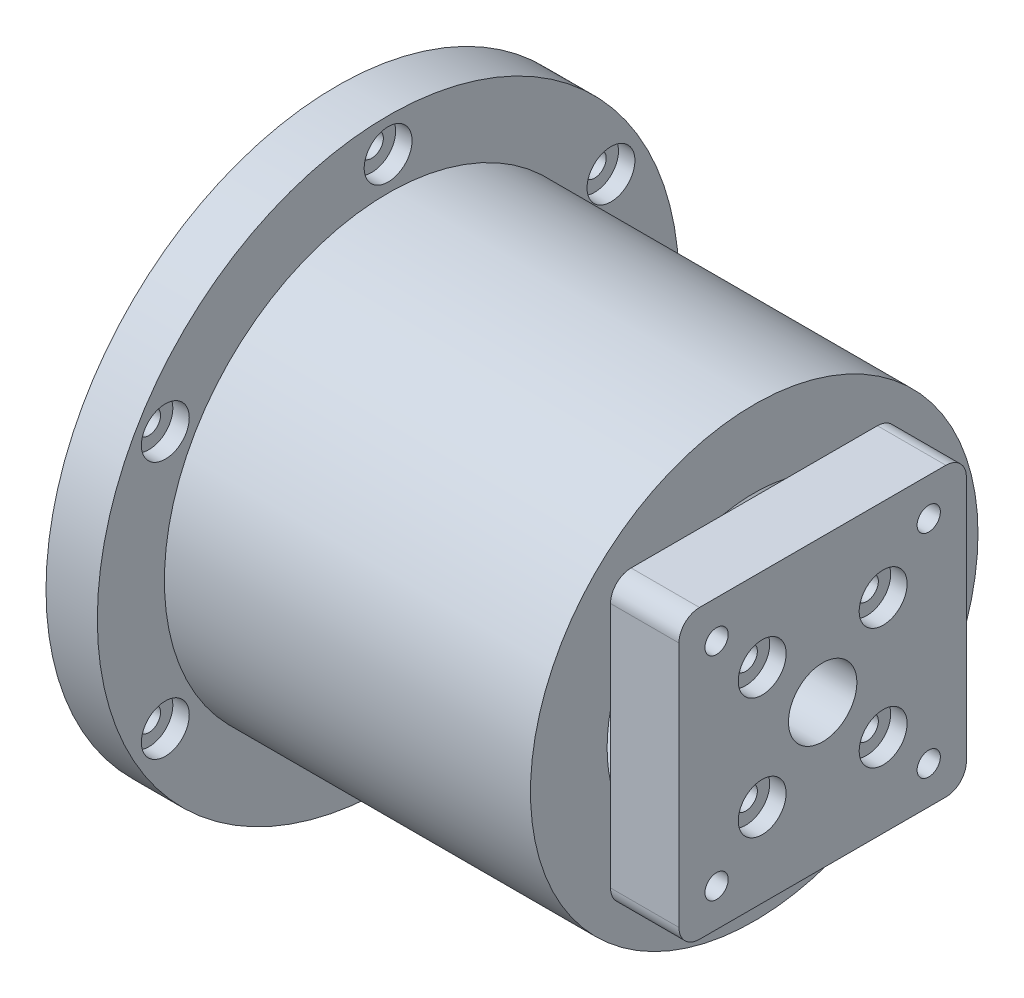
SolidWorks part; units mm, degrees
material "6063-T5"
ref_plane "Front" through (0, 0, 0) normal (0, 0, 1) x (1, 0, 0)
ref_plane "Top" through (0, 0, 0) normal (0, 1, 0) x (1, 0, 0)
ref_plane "Right" through (0, 0, 0) normal (1, 0, 0) x (0, 0, -1)
sketch "Croquis1" plane through (0, 0, 0) normal (1, 0, 0) x (0, 0, -1)
  line L6 (-18, -21) -> (18, -21)
  line L14 (-21, -18) -> (-21, 18)
  line L15 (-18, 21) -> (18, 21)
  line L16 (21, -18) -> (21, 18)
  line L17 (-21, -21) -> (21, 21) construction
  line L18 (-21, 21) -> (21, -21) construction
  circle A0 centre (0, 0) radius 5
  arc A1 (18, -21) -> (21, -18) centre (18, -18) ccw
  arc A2 (-18, -21) -> (-21, -18) centre (-18, -18) cw
  arc A3 (-21, 18) -> (-18, 21) centre (-18, 18) cw
  arc A4 (18, 21) -> (21, 18) centre (18, 18) cw
  point P0 (0, 0)
  dimension "D4" = 10
  dimension "D2" = 3
  dimension "D1" = 42
extrude "Saliente-Extruir1" add sketch "Croquis1" along normal blind 10
sketch "Croquis2" plane through (0, 0, 0) normal (-1, 0, 0) x (0, 0, 1)
  circle A0 centre (0, 0) radius 32.7
  dimension "D1" = 65.4
extrude "Saliente-Extruir2" add sketch "Croquis2" along normal blind 53.5 from surface contours A0 starting at plane "Right"
sketch "Croquis3" plane through (-53.5, 0, 0) normal (-1, 0, 0) x (0, 0, 1)
  circle A0 centre (0, 0) radius 21.5
  dimension "D1" = 43
extrude "Cortar-Extruir2" cut sketch "Croquis3" against normal up to surface (53.5 mm away) contours A0 up to face at (0, 0, 0)
hole_wizard "Refrentado para tornillo con cabeza troncocónica de M31" positions "Croquis4" profile "Croquis6" counterbore size "M3" standard "Ansi Metric" end condition up to next
sketch "Croquis4" plane through (10, 0, 0) normal (1, 0, 0) x (0, 0, -1)
  line L0 (0, 0) -> (-8.8388, 8.8388) construction
  line L3 (0, 50) -> (0, -50) construction
  point P0 (-8.8388, 8.8388)
  point P16 (8.8388, 8.8388)
  point P17 (8.8388, -8.8388)
  point P18 (-8.8388, -8.8388)
  dimension "D1" = 45
  dimension "D2" = 12.5
  dimension "D3" = 4
sketch "Croquis6" plane through (10, 8.8388, 8.8388) normal (0, 1, 0) x (0, 0, -1)
  line L0 (0, 0) -> (0, 10)
  line L1 (0, 10) -> (1.7, 10)
  line L3 (1.7, 10) -> (1.7, 2.4)
  line L4 (1.7, 2.4) -> (3.5, 2.4)
  line L5 (3.5, 2.4) -> (3.5, 0)
  line L7 (3.5, 0) -> (0, 0)
  line L11 (0, -6.35) -> (0, 107.95) construction
  dimension "Diámetro de taladro hasta el siguiente" = 3.4
  dimension "Profundidad de taladro hasta el siguiente" = 10
  dimension "Diámetro de refrentado" = 7
  dimension "Profundidad de refrentado" = 2.4
hole_wizard "Taladro de margen para M31" positions "Croquis7" profile "Croquis9" hole size "M3" standard "Ansi Metric"
sketch "Croquis7" plane through (10, 0, 0) normal (1, 0, 0) x (0, 0, -1)
  line L0 (0, 0) -> (15.5, 15.5) construction
  line L3 (0, 50) -> (0, -50) construction
  line L4 (50, 0) -> (-50, 0) construction
  point P0 (15.5, 15.5)
  point P17 (15.5, -15.5)
  point P18 (-15.5, -15.5)
  point P19 (-15.5, 15.5)
  dimension "D1" = 45
  dimension "D2" = 15.5
  dimension "D3" = 4
sketch "Croquis9" plane through (10, 15.5, -15.5) normal (0, 1, 0) x (0, 0, -1)
  line L0 (0, 0) -> (0, 17.0215)
  line L1 (0, 17.0215) -> (1.7, 16)
  line L2 (1.7, 16) -> (1.7, 0)
  line L5 (1.7, 0) -> (0, 0)
  line L10 (0, 17.0215) -> (-1.7, 16) construction
  line L11 (0, -6.35) -> (0, 107.95) construction
  dimension "Diámetro de taladro" = 3.4
  dimension "Profundidad de taladro" = 16
  dimension "Ángulo de perforador" = 118
sketch "Croquis11" plane through (-53.5, 0, 0) normal (-1, 0, 0) x (0, 0, 1)
  line L6 (-18.5, -21.5) -> (18.5, -21.5)
  line L14 (-21.5, -18.5) -> (-21.5, 18.5)
  line L15 (-18.5, 21.5) -> (18.5, 21.5)
  line L16 (21.5, -18.5) -> (21.5, 18.5)
  line L17 (-21.5, -21.5) -> (21.5, 21.5) construction
  line L18 (-21.5, 21.5) -> (21.5, -21.5) construction
  circle A0 centre (0, 0) radius 42.5
  arc A1 (-18.5, -21.5) -> (-21.5, -18.5) centre (-18.5, -18.5) cw
  arc A2 (18.5, -21.5) -> (21.5, -18.5) centre (18.5, -18.5) ccw
  arc A3 (18.5, 21.5) -> (21.5, 18.5) centre (18.5, 18.5) cw
  arc A4 (-21.5, 18.5) -> (-18.5, 21.5) centre (-18.5, 18.5) cw
  circle A5 centre (0, 0) radius 21.5 construction
  dimension "D1" = 85
  dimension "D3" = 3
extrude "Saliente-Extruir3" add sketch "Croquis11" along normal blind 7.5
hole_wizard "Taladro de margen para M32" positions "Croquis12" profile "Croquis13" hole size "M3" standard "Ansi Metric"
sketch "Croquis12" plane through (-53.5, 0, 0) normal (-1, 0, 0) x (0, 0, 1)
  line L0 (0, 0) -> (-17.075, 17.075) construction
  line L3 (0, -50) -> (0, 50) construction
  line L4 (50, 0) -> (-50, 0) construction
  point P0 (-17.075, 17.075)
  point P18 (17.075, 17.075)
  point P19 (17.075, -17.075)
  point P20 (-17.075, -17.075)
  dimension "D1" = 45
  dimension "D2" = 17.075
  dimension "D3" = 4
sketch "Croquis13" plane through (-53.5, 17.075, -17.075) normal (0, 1, 0) x (0, 0, 1)
  line L0 (0, 0) -> (0, 17.0215)
  line L1 (0, 17.0215) -> (1.7, 16)
  line L2 (1.7, 16) -> (1.7, 0)
  line L5 (1.7, 0) -> (0, 0)
  line L10 (0, 17.0215) -> (-1.7, 16) construction
  line L11 (0, -6.35) -> (0, 107.95) construction
  dimension "Diámetro de taladro" = 3.4
  dimension "Profundidad de taladro" = 16
  dimension "Ángulo de perforador" = 118
hole_wizard "Refrentado para tornillo con cabeza troncocónica de M32" positions "Croquis14" profile "Croquis16" counterbore size "M3" standard "Ansi Metric" end condition up to next
sketch "Croquis14" plane through (-53.5, 0, 0) normal (1, 0, 0) x (0, 0, -1)
  line L0 (0, 50) -> (0, -50) construction
  line L1 (0, 42.5) -> (0, 32.7) construction
  circle A0 centre (0, 0) radius 42.5 construction
  circle A1 centre (0, 0) radius 32.7 construction
  circle A2 centre (0, 0) radius 42.5 construction
  point P0 (0, 37.6)
  point P15 (0, 37.6)
  point P20 (32.5626, 18.8)
  point P21 (32.5626, -18.8)
  point P22 (0, -37.6)
  point P23 (-32.5626, -18.8)
  point P24 (-32.5626, 18.8)
  point P26 (-14.285, -33.3451)
  point P29 (0, 0)
  dimension "D2" = 37.6
  dimension "D1" = 6
sketch "Croquis16" plane through (-53.5, 37.6, 0) normal (0, 1, 0) x (0, 0, -1)
  line L0 (0, 0) -> (0, 7.5)
  line L1 (0, 7.5) -> (1.7, 7.5)
  line L3 (1.7, 7.5) -> (1.7, 2.4)
  line L4 (1.7, 2.4) -> (3.5, 2.4)
  line L5 (3.5, 2.4) -> (3.5, 0)
  line L7 (3.5, 0) -> (0, 0)
  line L11 (0, -6.35) -> (0, 107.95) construction
  dimension "Diámetro de taladro hasta el siguiente" = 3.4
  dimension "Profundidad de taladro hasta el siguiente" = 7.5
  dimension "Diámetro de refrentado" = 7
  dimension "Profundidad de refrentado" = 2.4
